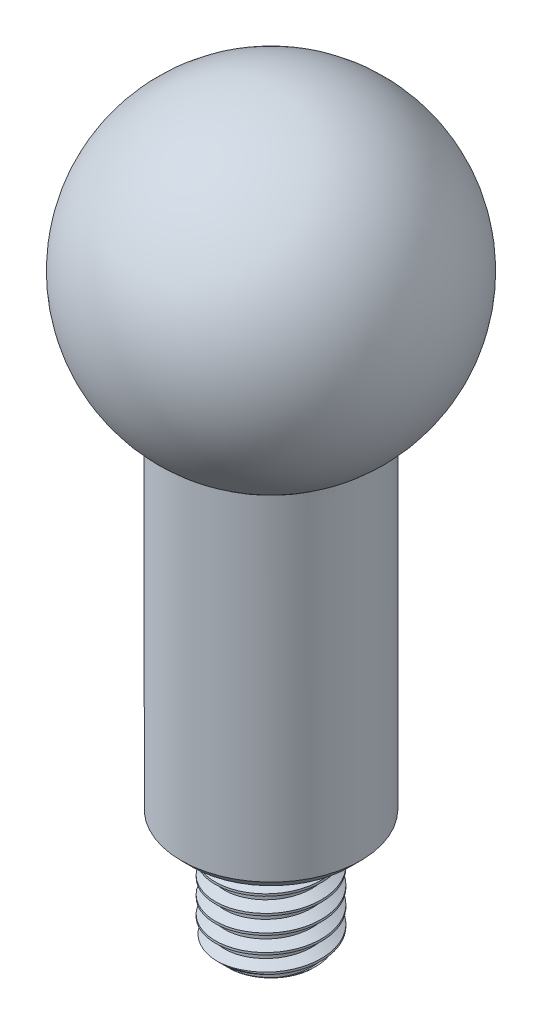
SolidWorks part; units mm, degrees
ref_plane "Front" through (0, 0, 0) normal (0, 0, 1) x (1, 0, 0)
ref_plane "Top" through (0, 0, 0) normal (0, 1, 0) x (1, 0, 0)
ref_plane "Right" through (0, 0, 0) normal (1, 0, 0) x (0, 0, -1)
sketch "Sketch1" plane through (0, 0, 0) normal (0, 0, 1) x (1, 0, 0)
  line L0 (0, 17.0191) -> (0, -9.6931) construction
  line L1 (0, -9.5928) -> (4.2345, -9.5928)
  line L2 (4.2345, -9.5928) -> (4.2345, 6.7169)
  line L3 (0, -9.5928) -> (0, 20.4072)
  circle A0 centre (0, 12.9072) radius 7.5 construction
  arc A1 (0, 20.4072) -> (4.2345, 6.7169) centre (0, 12.9072) cw
revolve "Revolve1" add sketch "Sketch1" angle 360 about L0
sketch "Sketch2" plane through (0, -9.5928, 0) normal (0, -1, 0) x (1, 0, 0)
  circle A0 centre (0, 0) radius 2.5
extrude "Boss-Extrude1" add sketch "Sketch2" along normal blind 5
chamfer "Chamfer1" distance 0.5 angle 45 2 edges at (0, -14.5928, -2.5) (0, -9.5928, 4.2345)
thread "Thread1" pitch 0.8 method cut profile "Thread Profile1" start angle 0, offset 0, length 6, pitch 0.8, diameter 5
ref_plane "Plane1" through (-2.5, -9.5928, 0) normal (0, 0, 1) x (-1, 0, 0)
sketch "Thread Profile1" plane through (-2.5, -9.5928, 0) normal (0, 0, 1) x (-1, 0, 0)
  line L0 (0, 0) -> (0, 0.8) construction
  line L11 (0, 0) -> (0, 0.7)
  line L12 (0, 0.7) -> (-0.433, 0.45)
  line L13 (-0.433, 0.45) -> (-0.433, 0.25)
  line L15 (-0.433, 0.25) -> (0, 0)
  line L17 (-0.433, 0.35) -> (0, 0.35) construction
  point P2 (0, 0)
  dimension "Pitch" = 0.8
  dimension "Profile_Angle" = 60
  dimension "Profile_Land" = 0.2
  dimension "Profile_Height" = 0.433
